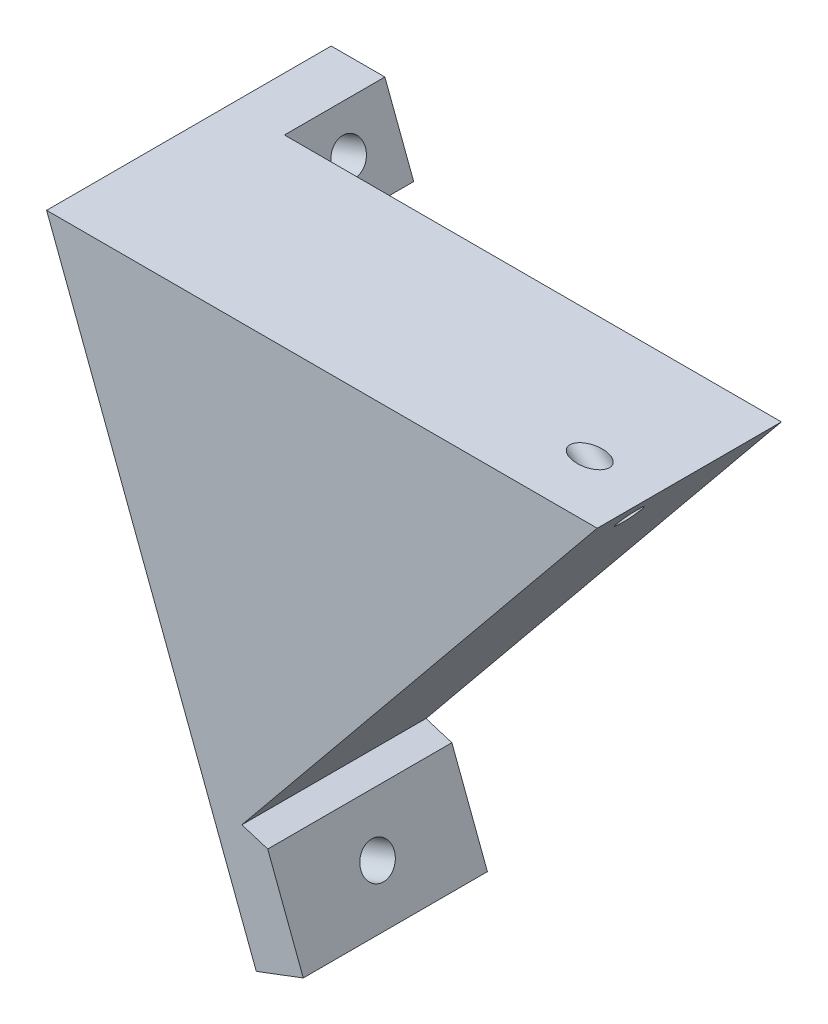
SolidWorks part; units mm, degrees
material "ABS"
ref_plane "Front Plane" through (0, 0, 0) normal (0, 0, 1) x (1, 0, 0)
ref_plane "Top Plane" through (0, 0, 0) normal (0, 1, 0) x (1, 0, 0)
ref_plane "Right Plane" through (0, 0, 0) normal (1, 0, 0) x (0, 0, -1)
sketch "Sketch1" plane through (0, 0, 0) normal (0, 0, 1) x (1, 0, 0)
  line L0 (-30.5498, 24.2413) -> (-9.7428, -30.7587)
  line L1 (-9.7428, -30.7587) -> (35.2388, 24.2413)
  line L2 (35.2388, 24.2413) -> (-30.5498, 24.2413)
  dimension "D1" = 55
  dimension "D2" = 55
  dimension "D3" = 60
extrude "Boss-Extrude1" add sketch "Sketch1" along normal blind 22
sketch "Sketch6" plane through (-18.7024, -7.0753, 0) normal (-0.9353, -0.3538, 0) x (0, 0, 1)
  line L0 (22, 33.4827) -> (22, -25.3215) construction
  line L1 (0, 33.4827) -> (-12, 33.4827)
  line L2 (0, 33.4827) -> (0, 21.4827)
  line L3 (0, 21.4827) -> (-12, 21.4827)
  line L4 (-12, 33.4827) -> (-12, 21.4827)
  line L5 (0, -25.3215) -> (22, -25.3215)
  line L6 (0, -25.3215) -> (0, -37.3215)
  line L7 (0, -37.3215) -> (22, -37.3215)
  line L8 (22, -25.3215) -> (22, -37.3215)
  dimension "D1" = 12
  dimension "D2" = 12
  dimension "D3" = 0
  dimension "D4" = 12
extrude "Boss-Extrude4" add sketch "Sketch6" against normal blind 6
sketch "Sketch8" plane through (0, 0, 0) normal (0, 0, -1) x (-1, 0, 0)
  line L0 (9.7428, -30.7587) -> (4.1309, -28.6356)
  line L1 (4.1309, -28.6356) -> (7.2207, -27.6748)
  line L2 (9.7428, -30.7587) -> (-35.2388, 24.2413) construction
  line L3 (7.2207, -27.6748) -> (9.7428, -30.7587)
extrude "Boss-Extrude5" add sketch "Sketch8" against normal up to vertex (22 mm away) up to point (35.2388, 24.2413, 22)
sketch "Sketch9" plane through (-13.0906, -4.9523, 0) normal (0.9353, 0.3538, 0) x (0, 0, -1)
  line L2 (12, 21.4827) -> (0, 21.4827) construction
  line L3 (0, -37.3215) -> (-22, -37.3215) construction
  line L4 (-22, -37.3215) -> (-22, -25.3215) construction
  circle A0 centre (6, 26.4827) radius 2
  circle A1 centre (-11, -31.3215) radius 2
  point P9 (6, 21.4827)
  point P12 (-11, -37.3215)
  point P15 (-22, -31.3215)
  dimension "D1" = 4
  dimension "D2" = 4
  dimension "D3" = 5
  dimension "D4" = 0
  dimension "D5" = 0
  dimension "D6" = 0
extrude "Cut-Extrude9" cut sketch "Sketch9" against normal blind 6
sketch "Sketch10" plane through (9.2356, -7.5533, 0) normal (0.7741, -0.6331, 0) x (0, 0, -1)
  line L0 (-22, 41.0739) -> (0, 41.0739) construction
  line L2 (-22, -25.9939) -> (-22, 41.0739) construction
  circle A0 centre (-15, 36.0739) radius 1.5
  dimension "D1" = 3
  dimension "D2" = 5
  dimension "D3" = 7
extrude "Cut-Extrude10" cut sketch "Sketch10" against normal blind 36
sketch "Sketch11" plane through (0, 0, 0) normal (0, 0, 1) x (1, 0, 0)
  line L0 (-30.5498, 24.2413) -> (-24.1348, 24.2413)
  line L1 (-24.1348, 24.2413) -> (-24.938, 26.3644)
  line L2 (-24.938, 26.3644) -> (-30.5498, 24.2413)
extrude "Cut-Extrude11" cut sketch "Sketch11" against normal blind 36
